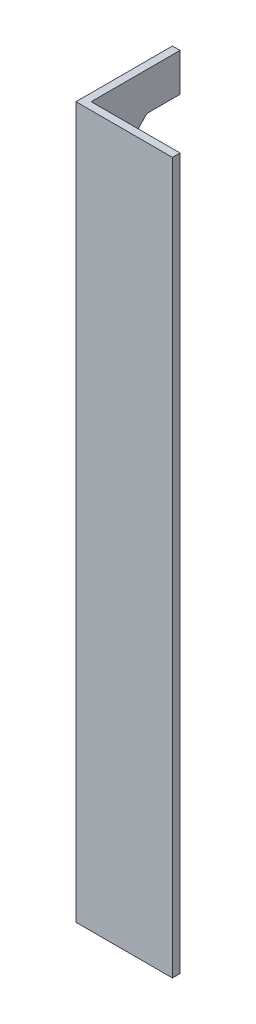
SolidWorks part; units mm, degrees
ref_plane "Alzado" through (0, 0, 0) normal (0, 0, 1) x (1, 0, 0)
ref_plane "Planta" through (0, 0, 0) normal (0, 1, 0) x (1, 0, 0)
ref_plane "Vista lateral" through (0, 0, 0) normal (1, 0, 0) x (0, 0, -1)
sketch "Croquis1" plane through (0, 0, 0) normal (0, 1, 0) x (1, 0, 0)
  line L0 (0, 0) -> (0, 38)
  line L1 (0, 0) -> (38, 0)
  line L2 (3, 3) -> (38, 3)
  line L3 (3, 3) -> (3, 38)
  line L4 (0, 38) -> (3, 38)
  line L5 (38, 3) -> (38, 0)
  dimension "D1" = 38
  dimension "D2" = 3
extrude "Saliente-Extruir1" add sketch "Croquis1" along normal blind 280
sketch "Croquis2" plane through (0, 0, 0) normal (-1, 0, 0) x (0, 0, 1)
  line L0 (-15, 0) -> (-15, 280) construction
  line L1 (-38, 0) -> (0, 0) construction
  line L2 (-38, 280) -> (0, 280) construction
  line L3 (-38, 280) -> (-38, 0) construction
  line L4 (0, 280) -> (0, 0) construction
  line L5 (-38, 15) -> (-15, 15)
  line L6 (-38, 280) -> (-38, 0) construction
  line L7 (-15, 15) -> (-15, 265)
  line L8 (-15, 265) -> (-38, 265)
  line L9 (-38, 15) -> (-38, 265)
  dimension "D1" = 15
  dimension "D2" = 15
  dimension "D3" = 15
extrude "Cortar-Extruir1" cut sketch "Croquis2" against normal up to surface (3 mm away) up to face at (3, 140, -20.5)
chamfer "Chaflán1" distance 10 angle 45 2 edges at (1.5, 15, -15) (1.5, 265, -15)
